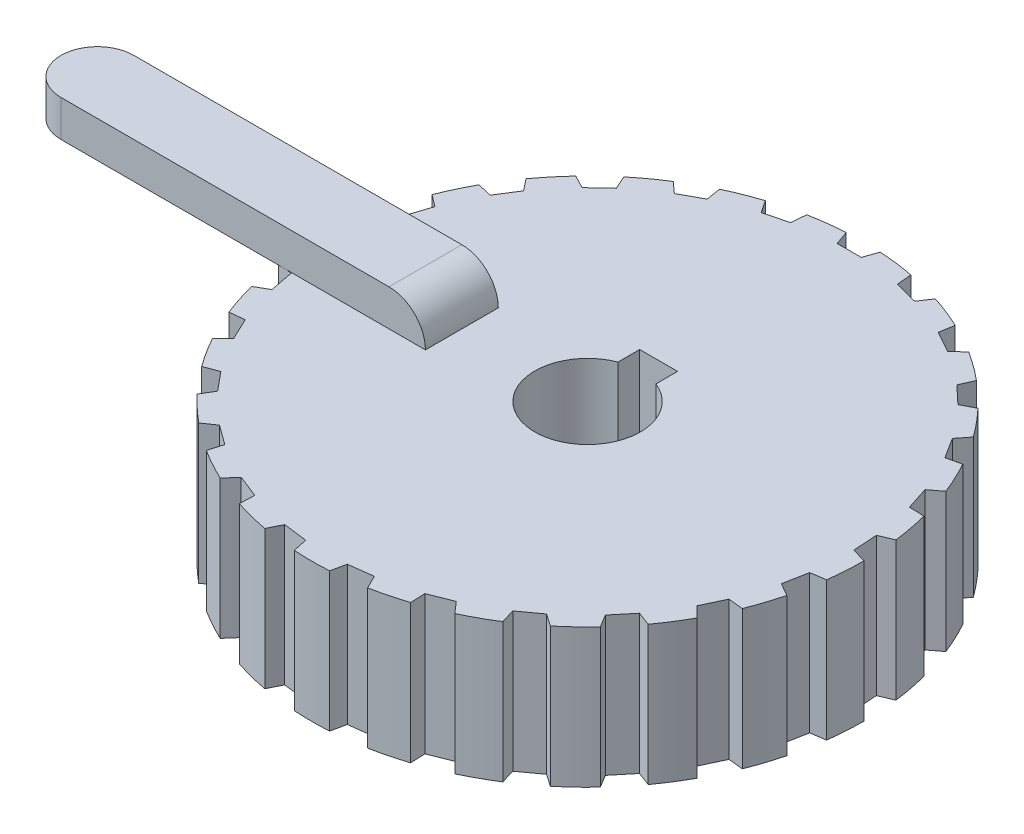
SolidWorks part; units mm, degrees
ref_plane "Front Plane" through (0, 0, 0) normal (0, 0, 1) x (1, 0, 0)
ref_plane "Top Plane" through (0, 0, 0) normal (0, 1, 0) x (1, 0, 0)
ref_plane "Right Plane" through (0, 0, 0) normal (1, 0, 0) x (0, 0, -1)
sketch "Sketch5" plane through (0, 0, 0) normal (0, 1, 0) x (1, 0, 0)
  circle A0 centre (0, 0) radius 37.8968
extrude "Boss-Extrude2" add sketch "Sketch5" along normal blind 19.05
sketch "Sketch8" plane through (0, 19.05, 0) normal (0, 1, 0) x (1, 0, 0)
  line L0 (0, 37.8968) -> (2.36, 37.8968)
  line L1 (0, 37.8968) -> (-2.36, 37.8968)
  line L5 (0, 35.8968) -> (-1.66, 35.8968)
  line L6 (0, 35.8968) -> (1.66, 35.8968)
  line L7 (-2.36, 37.8968) -> (-1.66, 35.8968)
  line L8 (2.36, 37.8968) -> (1.66, 35.8968)
  point P0 (0, 37.8968)
  dimension "D1" = 1.66
  dimension "D2" = 1.66
  dimension "D3" = 2
  dimension "D4" = 2.36
  dimension "D5" = 2.36
extrude "Cut-Extrude1" cut sketch "Sketch8" against normal blind 22.05
pattern_circular "CirPattern1" count 25 over 360 about axis through (0, 19.05, 0) along (0, 1, 0) of "Cut-Extrude1"
sketch "Sketch9" plane through (0, 19.05, 0) normal (0, 1, 0) x (1, 0, 0)
  line L0 (0, 7.25) -> (2.6, 7.25)
  line L1 (0, 7.25) -> (-2.6, 7.25)
  line L2 (-2.6, 7.25) -> (-2.6, 6.7678)
  line L3 (2.6, 7.25) -> (2.6, 6.7678)
  line L4 (-2.6, 7.25) -> (-2.6, 9.75)
  line L5 (-2.6, 9.75) -> (2.6, 9.75)
  line L6 (2.6, 9.75) -> (2.6, 7.25)
  circle A0 centre (0, 0) radius 7.25
extrude "Cut-Extrude2" cut sketch "Sketch9" against normal blind 25.4 contours A0 | L6 L5 L4 L1 L0 | A0 L1 L2 | A0 L3 L0 region at (0, 19.05, -8.5) region at (-1.9544, 19.05, -7.1062) region at (1.9544, 19.05, -7.1062) region at (0, 19.05, 0)
sketch "Sketch10" plane through (0, 19.05, 0) normal (0, 1, 0) x (1, 0, 0)
  line L2 (-7.25, 0) -> (-17.25, 0)
  line L7 (-17.25, 0) -> (-17.25, 5)
  line L8 (-17.25, 0) -> (-17.25, -5)
  line L9 (-17.25, 5) -> (-67.25, 5)
  line L10 (-67.25, 5) -> (-67.25, -5)
  line L11 (-67.25, -5) -> (-17.25, -5)
  arc A1 (-2.6, 6.7678) -> (2.6, 6.7678) centre (0, 0) ccw construction
  arc A2 (-67.25, 5) -> (-67.25, -5) centre (-67.25, 0) ccw
extrude "Boss-Extrude4" add sketch "Sketch10" along normal blind 5 contours L10 A2 | L10 L11 L8 L7 L9 region at (-42.25, 19.05, 0) region at (-69.3721, 19.05, 0)
fillet "Fillet2" radius 5 1 edges at (-17.25, 24.05, 0)
